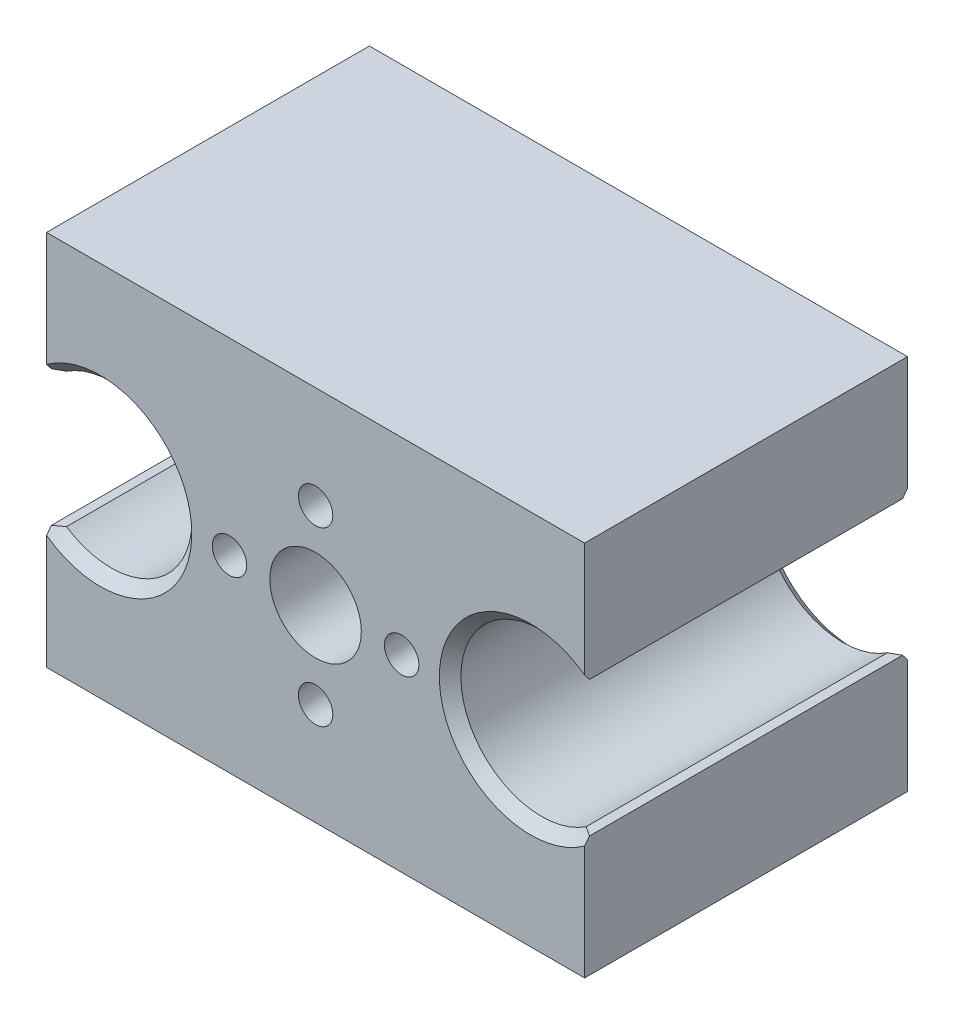
SolidWorks part; units mm, degrees
ref_plane "前视基准面" through (0, 0, 0) normal (0, 0, 1) x (1, 0, 0)
ref_plane "上视基准面" through (0, 0, 0) normal (0, 1, 0) x (1, 0, 0)
ref_plane "右视基准面" through (0, 0, 0) normal (1, 0, 0) x (0, 0, -1)
other "Configuration Table"
sketch "草图1" plane through (0, 0, 0) normal (0, 0, 1) x (1, 0, 0)
  line L1 (-25, -17.5) -> (25, -17.5)
  line L2 (-25, -17.5) -> (-25, 17.5)
  line L3 (-25, 17.5) -> (25, 17.5)
  line L4 (25, -17.5) -> (25, 17.5)
  line L5 (-25, -17.5) -> (25, 17.5) construction
  line L6 (-25, 17.5) -> (25, -17.5) construction
  point P0 (0, 0)
  dimension "D1" = 50
  dimension "D2" = 35
extrude "凸台-拉伸1" add sketch "草图1" along normal blind 30
hole_wizard "光轴孔" positions "草图2" profile "草图3" legacy end condition through all
sketch "草图2" plane through (0, 0, 30) normal (0, 0, 1) x (1, 0, 0)
  point P0 (0, 0)
sketch "草图3" plane through (0, 0, 30) normal (1, 0, 0) x (0, -1, 0)
  line L0 (0, 0) -> (0, 30)
  line L1 (0, 30) -> (4.25, 30)
  line L2 (4.25, 30) -> (4.25, 0)
  line L3 (4.25, 0) -> (0, 0)
  line L4 (0, 110) -> (0, -10) construction
  dimension "直径" = 8.5
  dimension "深度" = 30
hole_wizard "光轴座螺丝孔" positions "草图4" profile "草图5" legacy end condition through all
sketch "草图4" plane through (0, 0, 30) normal (0, 0, 1) x (1, 0, 0)
  point P0 (8, 0)
  point P4 (0, 8)
  point P6 (-8, 0)
  point P8 (0, -8)
  dimension "D1" = 8
  dimension "D2" = 8
  dimension "D3" = 8
  dimension "D4" = 8
sketch "草图5" plane through (8, 0, 30) normal (1, 0, 0) x (0, -1, 0)
  line L0 (0, 0) -> (0, 30)
  line L1 (0, 30) -> (1.6, 30)
  line L2 (1.6, 30) -> (1.6, 0)
  line L3 (1.6, 0) -> (0, 0)
  line L4 (0, 110) -> (0, -10) construction
  dimension "直径" = 3.2
  dimension "深度" = 30
hole_wizard "直线轴承座孔" positions "草图6" profile "草图7" legacy end condition through all
sketch "草图6" plane through (0, 0, 30) normal (0, 0, 1) x (1, 0, 0)
  point P0 (20, 0)
  point P2 (-20, 0)
  dimension "D1" = 20
  dimension "D2" = 20
sketch "草图7" plane through (20, 0, 30) normal (1, 0, 0) x (0, -1, 0)
  line L0 (0, 0) -> (0, 30)
  line L1 (0, 30) -> (7.5, 30)
  line L2 (7.5, 30) -> (7.5, 0)
  line L3 (7.5, 0) -> (0, 0)
  line L4 (0, 110) -> (0, -10) construction
  dimension "直径" = 15
  dimension "深度" = 30
chamfer "倒角1" distance 1 angle 45 8 edges at (25, -5.5902, 15) (12.5, 0, 30) (25, 5.5902, 15) (12.5, 0, 0) (-12.5, 0, 30) (-12.5, 0, 0) (-25, 5.5902, 15) (-25, -5.5902, 15) first distance on face at (18.75, 0, 15) first distance on face at (-18.75, 0, 15)
hole_wizard "孔1" positions "草图8" profile "草图9" legacy
sketch "草图8" plane through (0, 0, 0) normal (0, 0, -1) x (-1, 0, 0)
  point P0 (0, 0)
sketch "草图9" plane through (0, 0, 0) normal (1, 0, 0) x (0, 1, 0)
  line L0 (0, 0) -> (0, 12)
  line L1 (0, 12) -> (5.25, 12)
  line L2 (5.25, 12) -> (5.25, 0)
  line L3 (5.25, 0) -> (0, 0)
  line L4 (0, 110) -> (0, -10) construction
  dimension "直径" = 10.5
  dimension "深度" = 12
